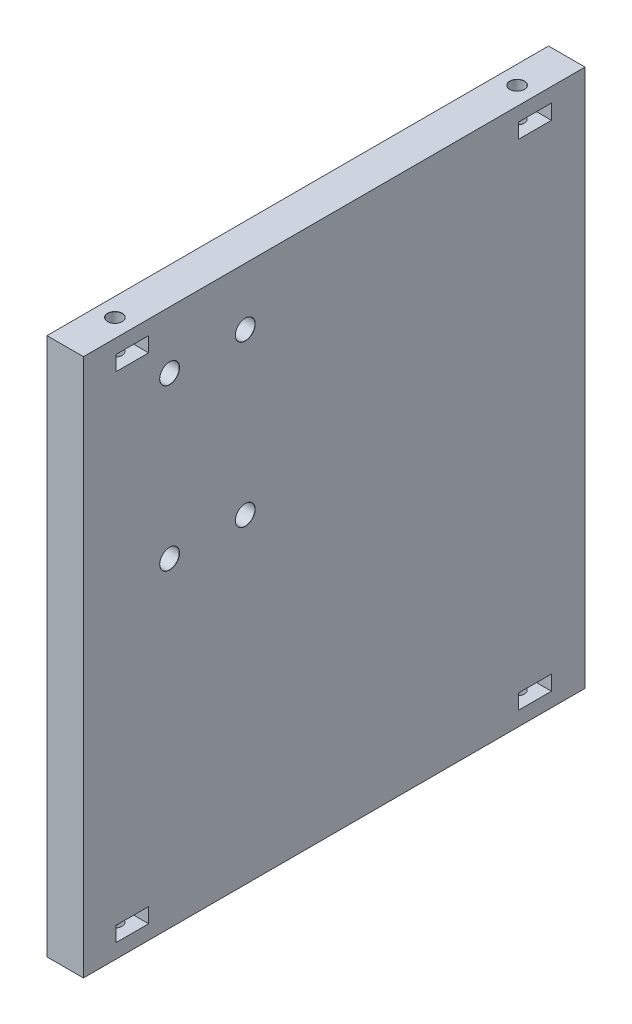
SolidWorks part; units mm, degrees
material "6061 Alloy"
ref_plane "Front Plane" through (0, 0, 0) normal (0, 0, 1) x (1, 0, 0)
ref_plane "Top Plane" through (0, 0, 0) normal (0, 1, 0) x (1, 0, 0)
ref_plane "Right Plane" through (0, 0, 0) normal (1, 0, 0) x (0, 0, -1)
sketch "Sketch1" plane through (0, 0, 0) normal (1, 0, 0) x (0, 0, -1)
  line L1 (-43.65, -46.825) -> (43.65, -46.825)
  line L2 (-43.65, -46.825) -> (-43.65, 46.825)
  line L3 (-43.65, 46.825) -> (43.65, 46.825)
  line L4 (43.65, -46.825) -> (43.65, 46.825)
  line L5 (-43.65, -46.825) -> (43.65, 46.825) construction
  line L6 (-43.65, 46.825) -> (43.65, -46.825) construction
  point P0 (0, 0)
extrude "Boss-Extrude1" add sketch "Sketch1" along normal blind 6.35
sketch "Sketch2" plane through (0, 46.825, 0) normal (0, 1, 0) x (1, 0, 0)
  line L0 (3.175, 43.65) -> (3.175, 35)
  line L1 (6.35, 43.65) -> (0, 43.65) construction
  line L2 (3.175, -43.65) -> (3.175, -35)
  line L3 (6.35, -43.65) -> (0, -43.65) construction
hole_wizard "Tap Drill for M3x0.5 Tap1" positions "Sketch3" profile "Sketch4" hole size "M3x0.5" standard "ANSI Metric"
sketch "Sketch3" plane through (0, 46.825, 0) normal (0, 1, 0) x (1, 0, 0)
  point P0 (3.175, 35)
  point P3 (3.175, -35)
sketch "Sketch4" plane through (3.175, 46.825, -35) normal (1, 0, 0) x (0, 0, 1)
  line L0 (0, 0) -> (0, 10.7511)
  line L1 (0, 10.7511) -> (1.25, 10)
  line L2 (1.25, 10) -> (1.25, 0.025)
  line L3 (1.25, 0.025) -> (1.275, 0)
  line L5 (1.275, 0) -> (0, 0)
  line L6 (-1.25, 0.025) -> (-1.275, 0) construction
  line L10 (0, 10.7511) -> (-1.25, 10) construction
  line L11 (0, -6.35) -> (0, 107.95) construction
  dimension "Hole Dia." = 2.5
  dimension "Hole Depth" = 10
  dimension "Near C'Sink Dia." = 2.55
  dimension "Near C'Sink Angle" = 90
  dimension "Drill Angle" = 118
sketch "Sketch5" plane through (0, -46.825, 0) normal (0, -1, 0) x (1, 0, 0)
  line L0 (3.175, 43.65) -> (3.175, 35)
  line L1 (3.175, -43.65) -> (3.175, -35)
  line L2 (6.35, -43.65) -> (0, -43.65) construction
hole_wizard "Tap Drill for M3x0.5 Tap2" positions "Sketch6" profile "Sketch7" hole size "M3x0.5" standard "ANSI Metric"
sketch "Sketch6" plane through (0, -46.825, 0) normal (0, -1, 0) x (-1, 0, 0)
  point P0 (-3.175, -35)
  point P3 (-3.175, 35)
sketch "Sketch7" plane through (3.175, -46.825, 35) normal (1, 0, 0) x (0, 0, -1)
  line L0 (0, 0) -> (0, 10)
  line L1 (0, 10) -> (1.25, 9.2489)
  line L2 (1.25, 9.2489) -> (1.25, 0.025)
  line L3 (1.25, 0.025) -> (1.275, 0)
  line L5 (1.275, 0) -> (0, 0)
  line L6 (-1.25, 0.025) -> (-1.275, 0) construction
  line L10 (0, 10) -> (-1.25, 9.2489) construction
  line L11 (0, -6.35) -> (0, 107.95) construction
  dimension "Hole Dia." = 2.5
  dimension "Hole Depth" = 10
  dimension "Near C'Sink Dia." = 2.55
  dimension "Near C'Sink Angle" = 90
  dimension "Drill Angle" = 118
sketch "Sketch11" plane through (6.35, 0, 0) normal (1, 0, 0) x (0, 0, -1)
  line L0 (-43.65, 46.825) -> (-43.65, 36.825)
  line L1 (-43.65, 46.825) -> (-43.65, -46.825) construction
  line L2 (-43.65, 36.825) -> (-28.65, 36.825)
  line L3 (-28.65, 36.825) -> (-28.65, 8.885)
  line L4 (-28.65, 8.885) -> (-15.48, 8.885)
  line L5 (-15.48, 8.885) -> (-15.48, 36.825)
hole_wizard "M3 Clearance Hole2" positions "Sketch12" profile "Sketch13" hole size "M3" standard "ANSI Metric" end condition through all
sketch "Sketch12" plane through (6.35, 0, 0) normal (1, 0, 0) x (0, 0, -1)
  point P0 (-28.65, 36.825)
  point P3 (-15.48, 36.825)
  point P6 (-15.48, 8.885)
  point P9 (-28.65, 8.885)
sketch "Sketch13" plane through (6.35, 36.825, 28.65) normal (0, 1, 0) x (0, 0, -1)
  line L0 (0, 0) -> (0, 6.35)
  line L1 (0, 6.35) -> (1.7, 6.35)
  line L2 (1.7, 6.35) -> (1.7, 0.025)
  line L3 (1.7, 0.025) -> (1.725, 0)
  line L5 (1.725, 0) -> (0, 0)
  line L6 (-1.7, 0.025) -> (-1.725, 0) construction
  line L11 (0, -6.35) -> (0, 107.95) construction
  dimension "Thru Hole Dia." = 3.4
  dimension "Thru Hole Depth" = 6.35
  dimension "Near C'Sink Dia." = 3.45
  dimension "Near C'Sink Angle" = 90
sketch "Sketch24" plane through (6.35, 0, 0) normal (1, 0, 0) x (0, 0, -1)
  line L0 (-43.65, -46.825) -> (43.65, -46.825) construction
  line L1 (-43.65, 46.825) -> (-43.65, -46.825) construction
  line L2 (-43.65, 46.825) -> (-43.65, -46.825) construction
  line L3 (43.65, -46.825) -> (43.65, 46.825) construction
  line L4 (32.1, -44.325) -> (37.8, -44.325)
  line L5 (32.1, -44.325) -> (32.1, -41.725)
  line L6 (32.1, -41.725) -> (37.8, -41.725)
  line L7 (37.8, -44.325) -> (37.8, -41.725)
  line L8 (32.1, -44.325) -> (37.8, -41.725) construction
  line L9 (32.1, -41.725) -> (37.8, -44.325) construction
  line L10 (-38, -44.325) -> (-32.3, -44.325)
  line L11 (-38, -44.325) -> (-38, -41.725)
  line L12 (-38, -41.725) -> (-32.3, -41.725)
  line L13 (-32.3, -44.325) -> (-32.3, -41.725)
  line L14 (-38, -44.325) -> (-32.3, -41.725) construction
  line L15 (-38, -41.725) -> (-32.3, -44.325) construction
  line L16 (-38, 44.325) -> (-32.3, 44.325)
  line L17 (-38, 44.325) -> (-38, 41.725)
  line L18 (-38, 41.725) -> (-32.3, 41.725)
  line L19 (-32.3, 44.325) -> (-32.3, 41.725)
  line L20 (-38, 44.325) -> (-32.3, 41.725) construction
  line L21 (-38, 41.725) -> (-32.3, 44.325) construction
  line L22 (32.1, 44.325) -> (37.8, 44.325)
  line L23 (32.1, 44.325) -> (32.1, 41.725)
  line L24 (32.1, 41.725) -> (37.8, 41.725)
  line L25 (37.8, 44.325) -> (37.8, 41.725)
  line L26 (32.1, 44.325) -> (37.8, 41.725) construction
  line L27 (32.1, 41.725) -> (37.8, 44.325) construction
  line L28 (43.65, 46.825) -> (-43.65, 46.825) construction
  point P5 (-35.15, -43.025)
  point P7 (34.95, -43.025)
  point P8 (-35.1207, -17.2297)
  point P13 (-35.1207, -17.2297)
  point P18 (-35.15, 43.025)
  point P23 (34.95, 43.025)
  point P34 (-35.15, -44.325)
  point P38 (0, 0)
  point P39 (0, 0)
  point P40 (0, 0)
  dimension "D1" = 29.5953
  dimension "D2" = 8.5293
  dimension "D3" = 5.7
  dimension "D4" = 2.6
  dimension "D5" = 2.5
  dimension "D6" = 8.5
  dimension "D7" = 5.85
  dimension "D8" = 2.5
extrude "Cut-Extrude1" cut sketch "Sketch24" against normal through all
